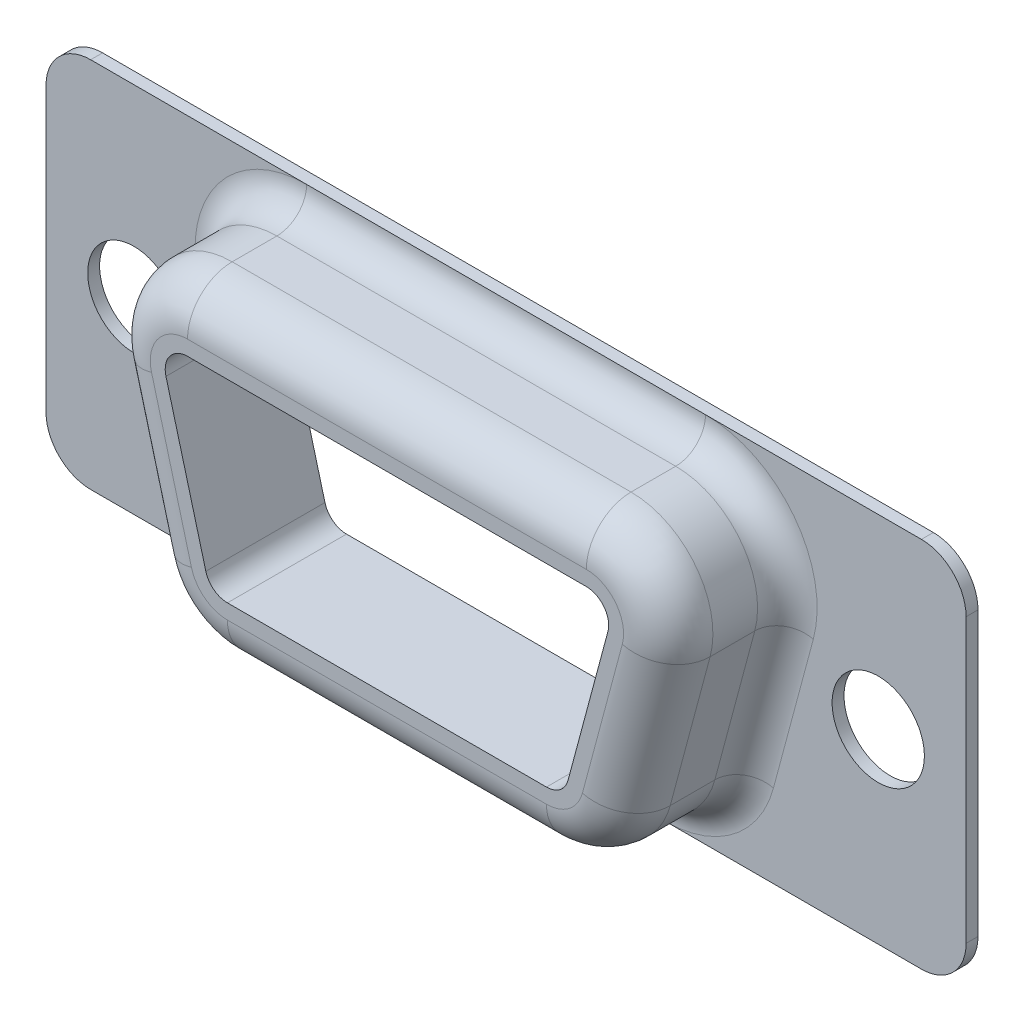
SolidWorks part; units mm, degrees
ref_plane "Front Plane" through (0, 0, 0) normal (0, 0, 1) x (1, 0, 0)
ref_plane "Top Plane" through (0, 0, 0) normal (0, 1, 0) x (1, 0, 0)
ref_plane "Right Plane" through (0, 0, 0) normal (1, 0, 0) x (0, 0, -1)
sketch "Sketch1" plane through (0, 0, 0) normal (0, 0, 1) x (1, 0, 0)
  line L0 (-135.2667, 0) -> (178.1738, 0) construction
  line L1 (0, 93.814) -> (0, -102.1772) construction
  line L2 (-8.146, 2.1118) -> (-6.8062, -2.8882)
  line L3 (-13.95, 6.25) -> (13.95, 6.25)
  line L4 (-15.45, 4.75) -> (-15.45, -4.75)
  line L5 (-13.95, -6.25) -> (13.95, -6.25)
  line L6 (15.45, 4.75) -> (15.45, -4.75)
  line L7 (-15.45, 6.25) -> (15.45, -6.25) construction
  line L8 (-15.45, -6.25) -> (15.45, 6.25) construction
  line L9 (-6.6971, 4) -> (6.75, 4)
  line L10 (8.146, 2.1118) -> (6.8062, -2.8882)
  line L11 (-5.3573, -4) -> (5.3573, -4)
  line L13 (-8.25, 4) -> (8.25, -4) construction
  line L14 (-8.25, -4) -> (8.25, 4) construction
  circle A0 centre (-12.5, 0) radius 1.55
  circle A1 centre (12.5, 0) radius 1.55
  arc A2 (8.146, 2.1118) -> (6.6971, 4) centre (6.6971, 2.5) ccw
  arc A3 (-8.146, 2.1118) -> (-6.6971, 4) centre (-6.6971, 2.5) cw
  arc A4 (5.3573, -4) -> (6.8062, -2.8882) centre (5.3573, -2.5) ccw
  arc A5 (-6.8062, -2.8882) -> (-5.3573, -4) centre (-5.3573, -2.5) ccw
  arc A6 (13.95, 6.25) -> (15.45, 4.75) centre (13.95, 4.75) cw
  arc A7 (13.95, -6.25) -> (15.45, -4.75) centre (13.95, -4.75) ccw
  arc A8 (-15.45, -4.75) -> (-13.95, -6.25) centre (-13.95, -4.75) ccw
  arc A9 (-13.95, 6.25) -> (-15.45, 4.75) centre (-13.95, 4.75) ccw
  point P5 (0, 0)
  point P14 (0, 0)
  dimension "D1" = 16.5
  dimension "D6" = 1.5
  dimension "D7" = 1.5
  dimension "D2" = 1.5
  dimension "D8" = 3.1
  dimension "D3" = 30.9
  dimension "D4" = 12.5
  dimension "D5" = 12.5
extrude "Boss-Extrude1" add sketch "Sketch1" along normal blind 0.4 contours L3 A9 L4 A8 L5 A7 L6 A6 A1 A0 A5 L2 A3 L9 A2 L10 A4 L11 region at (0, 5.9167, 0)
sketch "Sketch2" plane through (0, 0, 0.4) normal (0, 0, 1) x (1, 0, 0)
  line L0 (-5.3573, -3.25) -> (5.3573, -3.25)
  line L1 (6.0818, -2.6941) -> (7.4215, 2.3059)
  line L2 (6.6971, 3.25) -> (-6.6971, 3.25)
  line L3 (-7.4215, 2.3059) -> (-6.0818, -2.6941)
  line L9 (-9.3534, 1.7882) -> (-8.0136, -3.2118)
  line L10 (-5.3573, -5.25) -> (5.3573, -5.25)
  line L11 (8.0136, -3.2118) -> (9.3534, 1.7882)
  line L12 (6.6971, 5.25) -> (-6.6971, 5.25)
  line L13 (-9.3534, 1.7882) -> (-8.0136, -3.2118)
  line L14 (-5.3573, -5.25) -> (5.3573, -5.25)
  line L15 (8.0136, -3.2118) -> (9.3534, 1.7882)
  line L16 (6.6971, 5.25) -> (-6.6971, 5.25)
  line L21 (6.6971, 4) -> (-6.6971, 4)
  line L22 (6.8062, -2.8882) -> (8.146, 2.1118)
  line L23 (-5.3573, -4) -> (5.3573, -4)
  line L24 (-8.146, 2.1118) -> (-6.8062, -2.8882)
  line L25 (6.6971, 4) -> (-6.6971, 4) construction
  line L26 (6.8062, -2.8882) -> (8.146, 2.1118) construction
  line L27 (-5.3573, -4) -> (5.3573, -4) construction
  line L28 (-8.146, 2.1118) -> (-6.8062, -2.8882) construction
  arc A0 (5.3573, -3.25) -> (6.0818, -2.6941) centre (5.3573, -2.5) ccw
  arc A1 (7.4215, 2.3059) -> (6.6971, 3.25) centre (6.6971, 2.5) ccw
  arc A2 (-6.6971, 3.25) -> (-7.4215, 2.3059) centre (-6.6971, 2.5) ccw
  arc A3 (-6.0818, -2.6941) -> (-5.3573, -3.25) centre (-5.3573, -2.5) ccw
  arc A8 (-8.0136, -3.2118) -> (-5.3573, -5.25) centre (-5.3573, -2.5) ccw
  arc A9 (5.3573, -5.25) -> (8.0136, -3.2118) centre (5.3573, -2.5) ccw
  arc A10 (9.3534, 1.7882) -> (6.6971, 5.25) centre (6.6971, 2.5) ccw
  arc A11 (-6.6971, 5.25) -> (-9.3534, 1.7882) centre (-6.6971, 2.5) ccw
  arc A12 (-8.0136, -3.2118) -> (-5.3573, -5.25) centre (-5.3573, -2.5) ccw
  arc A13 (5.3573, -5.25) -> (8.0136, -3.2118) centre (5.3573, -2.5) ccw
  arc A14 (9.3534, 1.7882) -> (6.6971, 5.25) centre (6.6971, 2.5) ccw
  arc A15 (-6.6971, 5.25) -> (-9.3534, 1.7882) centre (-6.6971, 2.5) ccw
  arc A20 (-6.6971, 4) -> (-8.146, 2.1118) centre (-6.6971, 2.5) ccw
  arc A21 (8.146, 2.1118) -> (6.6971, 4) centre (6.6971, 2.5) ccw
  arc A22 (5.3573, -4) -> (6.8062, -2.8882) centre (5.3573, -2.5) ccw
  arc A23 (-6.8062, -2.8882) -> (-5.3573, -4) centre (-5.3573, -2.5) ccw
  arc A24 (-6.6971, 4) -> (-8.146, 2.1118) centre (-6.6971, 2.5) ccw construction
  arc A25 (8.146, 2.1118) -> (6.6971, 4) centre (6.6971, 2.5) ccw construction
  arc A26 (5.3573, -4) -> (6.8062, -2.8882) centre (5.3573, -2.5) ccw construction
  arc A27 (-6.8062, -2.8882) -> (-5.3573, -4) centre (-5.3573, -2.5) ccw construction
  dimension "D3" = 0.75
  dimension "D1" = 1.25
  dimension "D2" = 0
extrude "Boss-Extrude2" add sketch "Sketch2" along normal blind 4
fillet "Fillet1" radius 1 8 edges at (-8.6835, -0.7118, 0.4) (-8.8788, 4.1741, 0.4) (0, 5.25, 0.4) (8.8788, 4.1741, 0.4) (8.6835, -0.7118, 0.4) (7.0314, -4.6817, 0.4) (0, -5.25, 0.4) (-7.0314, -4.6817, 0.4)
fillet "Fillet2" radius 1.5 8 edges at (-8.8788, 4.1741, 4.4) (0, 5.25, 4.4) (8.8788, 4.1741, 4.4) (8.6835, -0.7118, 4.4) (7.0314, -4.6817, 4.4) (0, -5.25, 4.4) (-7.0314, -4.6817, 4.4) (-8.6835, -0.7118, 4.4)
